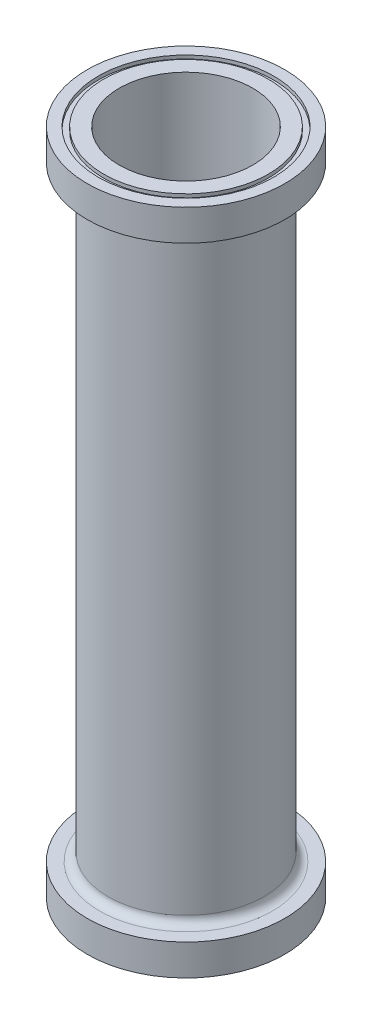
SolidWorks part; units mm, degrees
ref_plane "Front Plane" through (0, 0, 0) normal (0, 0, 1) x (1, 0, 0)
ref_plane "Top Plane" through (0, 0, 0) normal (0, 1, 0) x (1, 0, 0)
ref_plane "Right Plane" through (0, 0, 0) normal (1, 0, 0) x (0, 0, -1)
sketch "Sketch2" plane through (0, 0, 0) normal (0, 1, 0) x (1, 0, 0)
  circle A0 centre (0, 0) radius 38.1
  circle A1 centre (0, 0) radius 44.45
  dimension "D1" = 88.9
  dimension "D2" = 76.2
extrude "Base Cylinder" add sketch "Sketch2" along normal blind 381
sketch "Sketch3" plane through (0, 0, 0) normal (0, -1, 0) x (1, 0, 0)
  circle A0 centre (0, 0) radius 41.275
  circle A1 centre (0, 0) radius 56.388
  dimension "D1" = 112.776
extrude "Aft Flange" add sketch "Sketch3" against normal blind 17.78
sketch "Sketch4" plane through (0, 381, 0) normal (0, 1, 0) x (1, 0, 0)
  circle A0 centre (0, 0) radius 41.275
  circle A1 centre (0, 0) radius 56.388
  dimension "D1" = 112.776
extrude "Forward Flange" add sketch "Sketch4" against normal blind 17.78
sketch "Sketch6" plane through (0, 0, 0) normal (0, -1, 0) x (1, 0, 0)
  circle A0 centre (0, 0) radius 50.0761
  circle A1 centre (0, 0) radius 47.0027
  dimension "D1" = 100.1522
  dimension "D2" = 94.0054
extrude "O-Ring Slot 1" cut sketch "Sketch6" against normal blind 1.9812
sketch "Sketch7" plane through (0, 381, 0) normal (0, 1, 0) x (1, 0, 0)
  circle A0 centre (0, 0) radius 50.0761
  circle A1 centre (0, 0) radius 47.0027
  dimension "D1" = 100.1522
  dimension "D2" = 94.0054
extrude "O-Ring Slot 2" cut sketch "Sketch7" against normal blind 1.9812
sketch "Sketch8" plane through (0, 0, 0) normal (0, -1, 0) x (1, 0, 0)
  circle A0 centre (-59.9186, 0) radius 3.175
  circle A1 centre (-42.3688, 42.3688) radius 3.175
  circle A2 centre (0, 59.9186) radius 3.175
  circle A3 centre (42.3688, 42.3688) radius 3.175
  circle A4 centre (59.9186, 0) radius 3.175
  circle A5 centre (42.3688, -42.3688) radius 3.175
  circle A6 centre (0, -59.9186) radius 3.175
  circle A7 centre (-42.3688, -42.3688) radius 3.175
  point P36 (0, 0)
  dimension "D2" = 6.35
  dimension "D1" = 59.9186
  dimension "D3" = 8
extrude "Cut-Extrude4" [suppressed] cut sketch "Sketch8" against normal through all both and the other way through all
fillet "Fillet1" radius 4.7625 2 edges at (0, 17.78, -44.45) (0, 363.22, 44.45)
sketch "Sketch9" plane through (0, 381, 0) normal (0, 1, 0) x (1, 0, 0)
  line L0 (0, -76.2) -> (0, 76.2) construction
  line L1 (-32.6024, 78.7092) -> (32.6024, -78.7092) construction
  line L2 (-32.0538, -77.3847) -> (32.0538, 77.3847) construction
  circle A0 centre (0, 0) radius 59.9186 construction
  circle A1 centre (-22.9299, 55.3576) radius 3.175
  circle A2 centre (22.9299, -55.3576) radius 3.175
  circle A3 centre (22.9299, 55.3576) radius 3.175
  circle A4 centre (-22.9299, -55.3576) radius 3.175
  point P6 (0, 0)
  point P9 (0, 0)
  point P16 (0, 0)
  dimension "D1" = 119.8372
  dimension "D3" = 6.35
  dimension "D4" = 6.35
  dimension "D5" = 6.35
  dimension "D6" = 6.35
  dimension "D2" = 22.5
  dimension "D7" = 22.5
extrude "Cut-Extrude5" [suppressed] cut sketch "Sketch9" against normal blind 7.62
sketch "Sketch10" plane through (0, 0, 0) normal (0, -1, 0) x (1, 0, 0)
  line L0 (0, -76.2) -> (0, 76.2) construction
  line L1 (-33.7592, 81.5019) -> (33.7592, -81.5019) construction
  line L2 (-33.8465, -81.7128) -> (33.8465, 81.7128) construction
  circle A0 centre (0, 0) radius 59.9186 construction
  circle A1 centre (-22.9299, 55.3576) radius 3.175
  circle A2 centre (22.9299, -55.3576) radius 3.175
  circle A3 centre (22.9299, 55.3576) radius 3.175
  circle A4 centre (-22.9299, -55.3576) radius 3.175
  point P6 (0, 0)
  point P9 (0, 0)
  point P16 (0, 0)
  dimension "D1" = 119.8372
  dimension "D2" = 6.35
  dimension "D3" = 6.35
  dimension "D5" = 6.35
  dimension "D6" = 6.35
  dimension "D4" = 22.5
  dimension "D7" = 22.5
extrude "Cut-Extrude6" [suppressed] cut sketch "Sketch10" against normal blind 7.62
sketch "Sketch11" [suppressed] plane through (0, 373.38, 0) normal (0, 1, 0) x (1, 0, 0)
  circle A0 centre (-22.9299, 55.3576) radius 1.4097
  circle A1 centre (22.9299, 55.3576) radius 1.4097
  circle A2 centre (-22.9299, -55.3576) radius 1.4097
  circle A3 centre (22.9299, -55.3576) radius 1.4097
  dimension "D1" = 2.8194
  dimension "D2" = 2.8194
  dimension "D3" = 2.8194
  dimension "D4" = 2.8194
extrude "Cut-Extrude7" [suppressed] cut sketch "Sketch11" against normal up to next
sketch "Sketch12" [suppressed] plane through (0, 7.62, 0) normal (0, -1, 0) x (1, 0, 0)
  circle A0 centre (-22.9299, 55.3576) radius 1.4097
  circle A1 centre (22.9299, 55.3576) radius 1.4097
  circle A2 centre (-22.9299, -55.3576) radius 1.4097
  circle A3 centre (22.9299, -55.3576) radius 1.4097
  dimension "D1" = 2.8194
  dimension "D2" = 2.8194
  dimension "D3" = 2.8194
  dimension "D4" = 2.8194
extrude "Cut-Extrude8" [suppressed] cut sketch "Sketch12" against normal up to next
ref_plane "Plane1" through (-69.85, 0, 0) normal (1, 0, 0) x (0, 0, -1)
ref_plane "Plane3" through (69.85, 0, 0) normal (1, 0, 0) x (0, 0, -1)
ref_plane "Plane4" through (0, 372.11, 0) normal (0, 1, 0) x (1, 0, 0)
sketch "Sketch13" plane through (-69.85, 0, 0) normal (1, 0, 0) x (0, 0, -1)
  line L0 (62.0268, 372.11) -> (-62.0268, 372.11) construction
  circle A0 centre (0, 372.11) radius 2.3114
  dimension "D1" = 4.6228
extrude "Cut-Extrude10" [suppressed] cut sketch "Sketch13" along normal blind 6.35
sketch "Sketch14" [suppressed] plane through (69.85, 0, 0) normal (1, 0, 0) x (0, 0, -1)
  circle A0 centre (0, 372.11) radius 2.3114
  dimension "D1" = 4.6228
extrude "Cut-Extrude11" [suppressed] cut sketch "Sketch14" against normal blind 6.35
ref_axis "Axis1" [suppressed] through (63.5, 372.11, 0) along (1, 0, 0)
ref_axis "Axis2" [suppressed] through (-63.5, 372.11, 0) along (-1, 0, 0)
